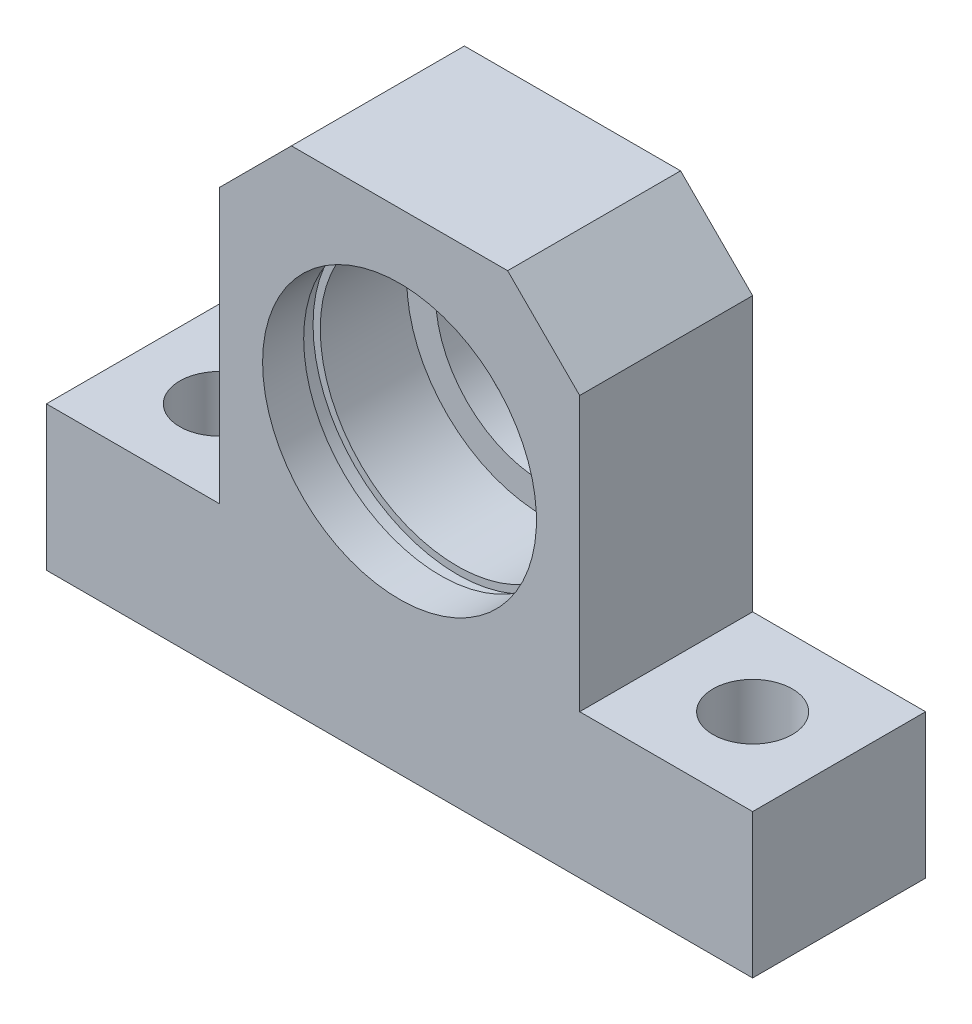
SolidWorks part; units mm, degrees
ref_plane "Front Plane" through (0, 0, 0) normal (0, 0, 1) x (1, 0, 0)
ref_plane "Top Plane" through (0, 0, 0) normal (0, 1, 0) x (1, 0, 0)
ref_plane "Right Plane" through (0, 0, 0) normal (1, 0, 0) x (0, 0, -1)
sketch "Sketch1" plane through (0, 0, 0) normal (0, 0, 1) x (1, 0, 0)
  line L0 (-12.5, 34) -> (12.5, 34)
  line L1 (12.5, 34) -> (12.5, 10)
  line L2 (12.5, 10) -> (24.5, 10)
  line L3 (24.5, 10) -> (24.5, 0)
  line L4 (24.5, 0) -> (-24.5, 0)
  line L5 (-24.5, 0) -> (-24.5, 10)
  line L6 (-24.5, 10) -> (-12.5, 10)
  line L7 (-12.5, 10) -> (-12.5, 34)
  line L8 (0, 34) -> (0, 0) construction
  point P12 (0, 20)
  dimension "L" = 49
  dimension "S" = 10
  dimension "L2" = 25
  dimension "H_s" = 20
  dimension "H" = 34
  dimension "MSM_6" = 14
extrude "Boss-Extrude1" add sketch "Sketch1" against normal blind 12
sketch "Sketch2" plane through (0, 0, 0) normal (1, 0, 0) x (0, 0, -1)
  line L0 (12, 20) -> (0, 20) construction
  line L1 (2.85, 29.5) -> (2.85, 30)
  line L2 (10, 29.5) -> (4, 29.5)
  line L3 (10, 29.5) -> (10, 27.5)
  line L4 (10, 27.5) -> (12, 27.5)
  line L5 (2.85, 30) -> (4, 30)
  line L6 (4, 30) -> (4, 29.5)
  line L7 (0, 29.5) -> (0, 20)
  line L8 (0, 20) -> (12, 20)
  line L9 (12, 20) -> (12, 27.5)
  line L11 (0, 10) -> (0, 34) construction
  line L12 (2.85, 29.5) -> (0, 29.5)
  line L13 (0, 10) -> (0, 34) construction
  line L14 (12, 10) -> (12, 34) construction
  dimension "D" = 19
  dimension "DH_s" = 15
  dimension "B" = 6
  dimension "H_s" = 20
  dimension "L1_s" = 2
  dimension "MSM_2" = 1.15
  dimension "MSM_1" = 20
revolve "Cut-Revolve1" cut sketch "Sketch2" angle 360 about L0
hole_wizard "Diameter Hole1" positions "Sketch4" profile "Sketch3" hole size "Ø5.5" standard "JIS" end condition through all
sketch "Sketch4" plane through (0, 10, 0) normal (0, 1, 0) x (1, 0, 0)
  line L10 (0, 0) -> (0, 12) construction
  line L11 (12.5, 12) -> (-12.5, 12) construction
  line L12 (-24.5, 6) -> (24.5, 6) construction
  line L13 (-24.5, 12) -> (-24.5, 0) construction
  line L14 (24.5, 12) -> (24.5, 0) construction
  point P0 (-18.5, 6)
  point P6 (18.5, 6)
  dimension "L1" = 37
  dimension "T/2" = 6
sketch "Sketch3" plane through (-18.5, 10, -6) normal (1, 0, 0) x (0, 0, 1)
  line L0 (0, 0) -> (0, 10)
  line L1 (0, 10) -> (2.75, 10)
  line L2 (2.75, 10) -> (2.75, 0)
  line L5 (2.75, 0) -> (0, 0)
  line L11 (0, 0) -> (0, 10) construction
  dimension "D1_s" = 5.5
  dimension "Thru Hole Depth" = 10
chamfer "Chamfer1" distance 5 angle 45 2 edges at (-12.5, 34, -6) (12.5, 34, -6)
chamfer "Chamfer2" [suppressed] distance 2 angle 45
